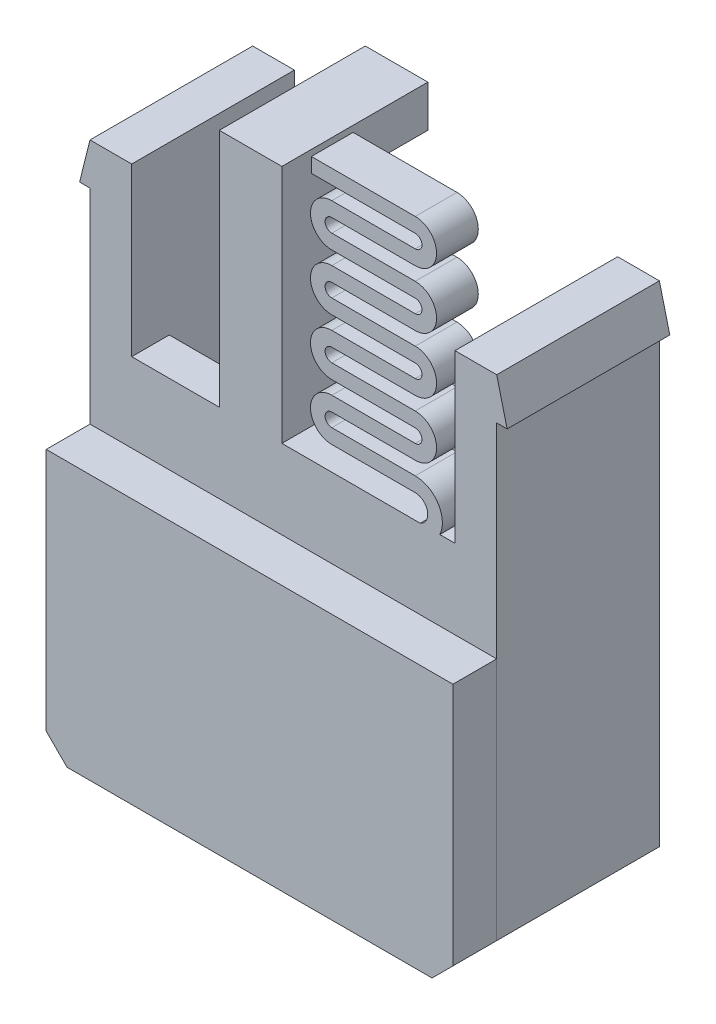
SolidWorks part; units mm, degrees
ref_plane "前视基准面" through (0, 0, 0) normal (0, 0, 1) x (1, 0, 0)
ref_plane "上视基准面" through (0, 0, 0) normal (0, 1, 0) x (1, 0, 0)
ref_plane "右视基准面" through (0, 0, 0) normal (1, 0, 0) x (0, 0, -1)
other "Configuration Table"
sketch "草图1" plane through (0, 0, 0) normal (0, 0, 1) x (1, 0, 0)
  line L0 (-63.9928, -19.7068) -> (-41.9928, -19.7068) construction
  line L1 (-62.7653, -7.0068) -> (-43.2653, -7.0068)
  line L2 (-62.7653, -7.0068) -> (-62.7653, -19.7068)
  line L3 (-62.7653, -19.7068) -> (-43.2653, -19.7068)
  line L4 (-43.2653, -7.0068) -> (-43.2653, -19.7068)
  dimension "D1" = 19.5
  dimension "D2" = 12.7
extrude "凸台-拉伸1" add sketch "草图1" along normal blind 2.1
sketch "草图2" plane through (0, 0, 0) normal (0, 0, -1) x (-1, 0, 0)
  line L1 (43.2653, -19.7068) -> (62.7653, -19.7068)
  line L2 (43.2653, -19.7068) -> (43.2653, 4.7932)
  line L3 (43.2653, 4.7932) -> (62.7653, 4.7932)
  line L4 (62.7653, -19.7068) -> (62.7653, 4.7932)
  dimension "D1" = 24.5
extrude "凸台-拉伸2" add sketch "草图2" along normal blind 7.8
sketch "草图3" plane through (0, 4.7932, 0) normal (0, 1, 0) x (1, 0, 0)
  line L0 (-62.7653, 7.8) -> (-43.2653, 7.8) construction
  line L1 (-60.7653, 7.8) -> (-45.2653, 7.8)
  line L2 (-60.7653, 7.8) -> (-60.7653, 1.8)
  line L3 (-60.7653, 1.8) -> (-45.2653, 1.8)
  line L4 (-45.2653, 7.8) -> (-45.2653, 1.8)
  line L5 (-62.7653, 7.8) -> (-62.7653, 0) construction
  line L6 (-43.2653, 7.8) -> (-43.2653, 0) construction
  dimension "D1" = 2
  dimension "D2" = 2
  dimension "D3" = 6
extrude "切除-拉伸1" cut sketch "草图3" against normal blind 23
sketch "草图4" plane through (0, 0, 0) normal (0, 0, 1) x (1, 0, 0)
  line L1 (-60.7653, 4.7932) -> (-45.2653, 4.7932)
  line L2 (-60.7653, 4.7932) -> (-60.7653, -3.2068)
  line L3 (-60.7653, -3.2068) -> (-45.2653, -3.2068)
  line L4 (-45.2653, 4.7932) -> (-45.2653, -3.2068)
  dimension "D1" = 8
extrude "切除-拉伸2" cut sketch "草图4" against normal up to next
sketch "草图5" plane through (0, 0, -7.8) normal (0, 0, -1) x (-1, 0, 0)
  line L0 (62.7653, 4.7932) -> (63.2653, 2.7932)
  line L1 (63.2653, 2.7932) -> (62.7653, 2.7932)
  line L2 (62.7653, -19.7068) -> (62.7653, 4.7932) construction
  line L3 (62.7653, 2.7932) -> (62.7653, 4.7932)
  line L4 (43.2653, 4.7932) -> (42.7653, 2.7932)
  line L5 (42.7653, 2.7932) -> (43.2653, 2.7932)
  line L6 (43.2653, 4.7932) -> (43.2653, -19.7068) construction
  line L7 (43.2653, 2.7932) -> (43.2653, 4.7932)
  dimension "D1" = 2
  dimension "D2" = 0.5
extrude "凸台-拉伸4" add sketch "草图5" against normal up to surface (7.8 mm away) up to face at (-53.0153, -0.1568, 0)
sketch "草图7" plane through (0, 0, 0) normal (0, 0, 1) x (1, 0, 0)
  line L0 (-47.1711, -1.7068) -> (-51.1711, -1.7068) construction
  line L1 (-60.7653, -3.2068) -> (-45.2653, -3.2068) construction
  line L2 (-47.1711, -0.3606) -> (-51.1711, -0.3606) construction
  line L3 (-47.1711, 0.9857) -> (-51.1711, 0.9857) construction
  line L4 (-47.1711, 2.3319) -> (-51.1711, 2.3319) construction
  line L5 (-47.1711, 3.6782) -> (-51.1711, 3.6782) construction
  line L6 (-47.1711, 5.0244) -> (-51.1711, 5.0244) construction
  line L7 (-47.1711, 6.3707) -> (-51.1711, 6.3707) construction
  line L8 (-47.1711, 7.7169) -> (-51.1711, 7.7169) construction
  line L9 (-47.1711, 9.0632) -> (-51.1711, 9.0632) construction
  line L10 (-47.1711, -1.3568) -> (-51.1711, -1.3568)
  line L11 (-47.1711, -0.7106) -> (-51.1711, -0.7106)
  line L12 (-47.1711, 1.3357) -> (-51.1711, 1.3357)
  line L13 (-47.1711, 1.9819) -> (-51.1711, 1.9819)
  line L14 (-47.1711, 4.0282) -> (-51.1711, 4.0282)
  line L15 (-47.1711, 4.6744) -> (-51.1711, 4.6744)
  line L16 (-47.1711, 6.7207) -> (-51.1711, 6.7207)
  line L17 (-47.1711, 7.3669) -> (-51.1711, 7.3669)
  line L18 (-47.1711, 9.4132) -> (-52.1509, 9.4132)
  line L19 (-47.1711, -2.0568) -> (-51.1711, -2.0568)
  line L20 (-47.1711, -0.0106) -> (-51.1711, -0.0106)
  line L21 (-47.1711, 0.6357) -> (-51.1711, 0.6357)
  line L22 (-47.1711, 2.6819) -> (-51.1711, 2.6819)
  line L23 (-47.1711, 3.3282) -> (-51.1711, 3.3282)
  line L24 (-47.1711, 5.3744) -> (-51.1711, 5.3744)
  line L25 (-47.1711, 6.0207) -> (-51.1711, 6.0207)
  line L26 (-47.1711, 8.0669) -> (-51.1711, 8.0669)
  line L27 (-47.1711, 8.7132) -> (-52.1509, 8.7132)
  line L28 (-47.1711, 9.0632) -> (-51.1407, 9.0632) construction
  line L29 (-47.1711, 8.7132) -> (-51.1407, 8.7132) construction
  line L30 (-47.1711, 9.4132) -> (-51.1407, 9.4132) construction
  line L31 (-72.3676, 9.4132) -> (-44.6127, 9.4132) construction
  line L32 (-52.1509, 9.4132) -> (-52.1509, 8.7132)
  line L33 (-46.9314, -3.2068) -> (-47.3969, -3.9371)
  arc A0 (-47.1711, -1.7068) -> (-46.3965, -3.2068) centre (-47.1711, -2.6568) cw construction
  arc A1 (-51.1711, -0.3606) -> (-51.1711, -1.7068) centre (-51.1711, -1.0337) ccw construction
  arc A2 (-47.1711, -0.3606) -> (-47.1711, 0.9857) centre (-47.1711, 0.3125) ccw construction
  arc A3 (-51.1711, 0.9857) -> (-51.1711, 2.3319) centre (-51.1711, 1.6588) cw construction
  arc A4 (-47.1711, 2.3319) -> (-47.1711, 3.6782) centre (-47.1711, 3.005) ccw construction
  arc A5 (-51.1711, 3.6782) -> (-51.1711, 5.0244) centre (-51.1711, 4.3513) cw construction
  arc A6 (-47.1711, 5.0244) -> (-47.1711, 6.3707) centre (-47.1711, 5.6975) ccw construction
  arc A7 (-51.1711, 6.3707) -> (-51.1711, 7.7169) centre (-51.1711, 7.0438) cw construction
  arc A8 (-47.1711, 7.7169) -> (-47.1711, 9.0632) centre (-47.1711, 8.39) ccw construction
  arc A9 (-47.1711, -1.3568) -> (-47.3969, -3.9371) centre (-47.1711, -2.6568) cw
  arc A10 (-51.1711, -0.7106) -> (-51.1711, -1.3568) centre (-51.1711, -1.0337) ccw
  arc A11 (-47.1711, -0.7106) -> (-47.1711, 1.3357) centre (-47.1711, 0.3125) ccw
  arc A12 (-51.1711, 1.3357) -> (-51.1711, 1.9819) centre (-51.1711, 1.6588) cw
  arc A13 (-47.1711, 1.9819) -> (-47.1711, 4.0282) centre (-47.1711, 3.005) ccw
  arc A14 (-51.1711, 4.0282) -> (-51.1711, 4.6744) centre (-51.1711, 4.3513) cw
  arc A15 (-47.1711, 4.6744) -> (-47.1711, 6.7207) centre (-47.1711, 5.6975) ccw
  arc A16 (-51.1711, 6.7207) -> (-51.1711, 7.3669) centre (-51.1711, 7.0438) cw
  arc A17 (-47.1711, 7.3669) -> (-47.1711, 9.4132) centre (-47.1711, 8.39) ccw
  arc A18 (-47.1711, -2.0568) -> (-46.9314, -3.2068) centre (-47.1711, -2.6568) cw
  arc A19 (-51.1711, -0.0106) -> (-51.1711, -2.0568) centre (-51.1711, -1.0337) ccw
  arc A20 (-47.1711, -0.0106) -> (-47.1711, 0.6357) centre (-47.1711, 0.3125) ccw
  arc A21 (-51.1711, 0.6357) -> (-51.1711, 2.6819) centre (-51.1711, 1.6588) cw
  arc A22 (-47.1711, 2.6819) -> (-47.1711, 3.3282) centre (-47.1711, 3.005) ccw
  arc A23 (-51.1711, 3.3282) -> (-51.1711, 5.3744) centre (-51.1711, 4.3513) cw
  arc A24 (-47.1711, 5.3744) -> (-47.1711, 6.0207) centre (-47.1711, 5.6975) ccw
  arc A25 (-51.1711, 6.0207) -> (-51.1711, 8.0669) centre (-51.1711, 7.0438) cw
  arc A26 (-47.1711, 8.0669) -> (-47.1711, 8.7132) centre (-47.1711, 8.39) ccw
  arc A27 (-47.1711, -1.7068) -> (-47.3361, -3.5924) centre (-47.1711, -2.6568) cw construction
  arc A28 (-47.1711, -2.0568) -> (-47.2753, -3.2477) centre (-47.1711, -2.6568) cw construction
  dimension "D1" = 4
  dimension "D2" = 1.5
  dimension "D4" = 0.35
  dimension "D5" = 0.35
  dimension "D3" = 9
extrude "凸台-拉伸5" add sketch "草图7" against normal blind 2
sketch "草图8" plane through (0, -3.2068, 0) normal (0, 1, 0) x (1, 0, 0)
  line L0 (-60.7653, 0) -> (-46.9314, 0) construction
  line L1 (-56.5653, 0) -> (-53.5653, 0)
  line L2 (-56.5653, 0) -> (-56.5653, 3)
  line L3 (-56.5653, 3) -> (-53.5653, 3)
  line L4 (-53.5653, 0) -> (-53.5653, 3)
  line L5 (-60.7653, 1.8) -> (-60.7653, 0) construction
  dimension "D1" = 4.2
  dimension "D2" = 3
  dimension "D3" = 3
extrude "凸台-拉伸6" add sketch "草图8" along normal blind 11.5 and the other way blind 4
sketch "草图9" plane through (0, 0, -3) normal (0, 0, -1) x (-1, 0, 0)
  line L0 (56.5653, -7.2068) -> (56.5653, 8.2932) construction
  line L1 (53.5653, 8.2932) -> (56.5653, 8.2932)
  line L2 (53.5653, 8.2932) -> (53.5653, 6.2932)
  line L3 (53.5653, 6.2932) -> (56.5653, 6.2932)
  line L4 (56.5653, 8.2932) -> (56.5653, 6.2932)
  dimension "D1" = 2
extrude "凸台-拉伸7" add sketch "草图9" along normal blind 4
chamfer "倒角1" distance 1 angle 45 2 edges at (-62.7653, -19.7068, -2.85) (-43.2653, -19.7068, -2.85)
split "分割1" bodies to split 114 resulting bodies 115 116 split by face at (-50.3799, 2.7132, 0)
